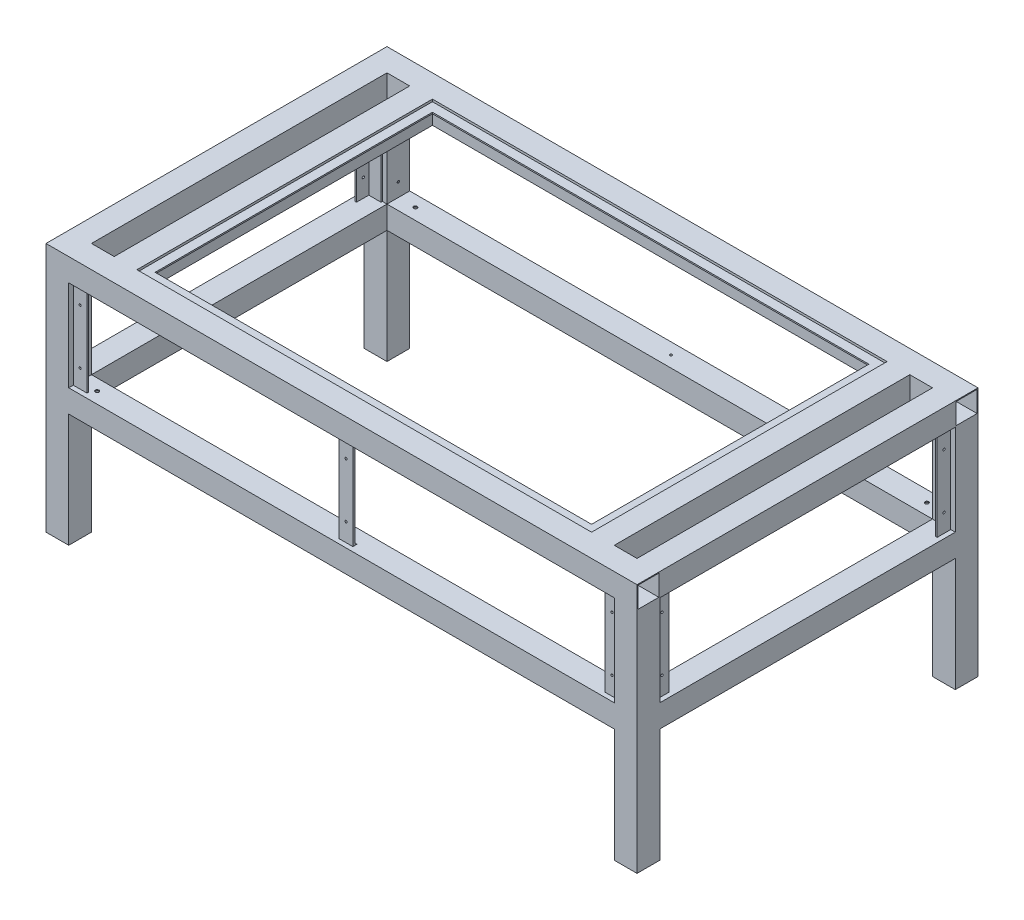
SolidWorks part; units mm, degrees
ref_plane "Plan de face" through (0, 0, 0) normal (0, 0, 1) x (1, 0, 0)
ref_plane "Plan de dessus" through (0, 0, 0) normal (0, 1, 0) x (1, 0, 0)
ref_plane "Plan de droite" through (0, 0, 0) normal (1, 0, 0) x (0, 0, -1)
sketch "Esquisse1" plane through (0, 0, 0) normal (0, 1, 0) x (1, 0, 0)
  line L1 (0, 0) -> (1300, 0)
  line L2 (0, 0) -> (0, 750)
  line L3 (0, 750) -> (1300, 750)
  line L4 (1300, 0) -> (1300, 750)
  line L5 (50, 700) -> (1250, 700)
  line L6 (50, 700) -> (50, 50)
  line L7 (50, 50) -> (1250, 50)
  line L8 (1250, 700) -> (1250, 50)
  dimension "D1" = 1300
  dimension "D2" = 750
  dimension "D3" = 50
  dimension "D4" = 50
  dimension "D5" = 50
  dimension "D6" = 50
extrude "Boss.-Extru.1" add sketch "Esquisse1" against normal blind 550
sketch "Esquisse2" plane through (0, 0, 0) normal (0, 0, 1) x (1, 0, 0)
  line L0 (0, 0) -> (1300, 0) construction
  line L1 (50, -50) -> (1250, -50)
  line L2 (50, -50) -> (50, -250)
  line L3 (50, -250) -> (1250, -250)
  line L4 (1250, -50) -> (1250, -250)
  line L5 (50, -300) -> (1250, -300)
  line L6 (50, -300) -> (50, -550)
  line L7 (50, -550) -> (1250, -550)
  line L8 (1250, -300) -> (1250, -550)
  line L9 (0, -550) -> (1300, -550) construction
  line L10 (1300, -550) -> (1300, 0) construction
  line L11 (0, -550) -> (0, 0) construction
  point P12 (1250, -425)
  dimension "D1" = 50
  dimension "D2" = 50
  dimension "D3" = 200
  dimension "D4" = 0
  dimension "D5" = 50
  dimension "D6" = 50
  dimension "D7" = 50
  dimension "D8" = 50
extrude "Enlèv. mat.-Extru.1" cut sketch "Esquisse2" against normal through all
sketch "Esquisse3" plane through (0, 0, 0) normal (-1, 0, 0) x (0, 0, 1)
  line L0 (-750, -550) -> (0, -550) construction
  line L1 (-700, -50) -> (-50, -50)
  line L2 (-700, -50) -> (-700, -250)
  line L3 (-700, -250) -> (-50, -250)
  line L4 (-50, -50) -> (-50, -250)
  line L5 (-700, -300) -> (-50, -300)
  line L6 (-700, -300) -> (-700, -550)
  line L7 (-700, -550) -> (-50, -550)
  line L8 (-50, -300) -> (-50, -550)
  line L9 (-750, 0) -> (0, 0) construction
  line L10 (0, -550) -> (0, 0) construction
  line L11 (-750, -550) -> (-750, 0) construction
  dimension "D1" = 50
  dimension "D2" = 50
  dimension "D3" = 50
  dimension "D4" = 50
  dimension "D5" = 50
  dimension "D6" = 200
  dimension "D7" = 50
extrude "Enlèv. mat.-Extru.2" cut sketch "Esquisse3" against normal through all
sketch "Esquisse4" plane through (0, 0, 0) normal (0, 1, 0) x (1, 0, 0)
  line L0 (1250, 700) -> (50, 700) construction
  line L1 (100, 700) -> (150, 700)
  line L2 (100, 700) -> (100, 50)
  line L3 (100, 50) -> (150, 50)
  line L4 (150, 700) -> (150, 50)
  line L5 (50, 50) -> (1250, 50) construction
  line L6 (50, 700) -> (50, 50) construction
  line L7 (1150, 700) -> (1200, 700)
  line L8 (1150, 700) -> (1150, 50)
  line L9 (1150, 50) -> (1200, 50)
  line L10 (1200, 700) -> (1200, 50)
  line L11 (1250, 50) -> (1250, 700) construction
  dimension "D1" = 50
  dimension "D2" = 50
  dimension "D3" = 50
  dimension "D4" = 50
extrude "Boss.-Extru.2" add sketch "Esquisse4" against normal blind 50 separate body
sketch "Esquisse18" plane through (0, -250, 0) normal (0, 1, 0) x (1, 0, 0)
  line L0 (50, 0) -> (1250, 0) construction
  line L1 (50, 750) -> (1250, 750) construction
  line L2 (1250, 750) -> (1250, 700) construction
  line L3 (50, 750) -> (50, 700) construction
  line L4 (1250, 50) -> (1250, 0) construction
  line L5 (50, 50) -> (50, 0) construction
  circle A0 centre (1212.5, 25) radius 4
  circle A1 centre (87.5, 25) radius 4
  circle A2 centre (87.5, 725) radius 4
  circle A3 centre (1212.5, 725) radius 4
  dimension "D1" = 8
  dimension "D2" = 8
  dimension "D3" = 8
  dimension "D4" = 8
  dimension "D5" = 1125
  dimension "D6" = 1125
  dimension "D7" = 25
  dimension "D8" = 25
  dimension "D9" = 25
  dimension "D10" = 25
  dimension "D11" = 700
  dimension "D12" = 700
  dimension "D13" = 37.5
  dimension "D14" = 37.5
  dimension "D15" = 37.5
  dimension "D16" = 37.5
extrude "Enlèv. mat.-Extru.5" cut sketch "Esquisse18" against normal blind 80
sketch "Esquisse19" plane through (0, -300, 0) normal (0, -1, 0) x (-1, 0, 0)
  circle A0 centre (-1212.5, 725) radius 15
  circle A1 centre (-87.5, 725) radius 15
  circle A2 centre (-87.5, 25) radius 15
  circle A3 centre (-1212.5, 25) radius 15
  dimension "D1" = 30
  dimension "D2" = 30
  dimension "D3" = 30
  dimension "D4" = 30
extrude "Enlèv. mat.-Extru.6" cut sketch "Esquisse19" against normal blind 48
sketch "Esquisse20" plane through (0, 0, 0) normal (-1, 0, 0) x (0, 0, 1)
  line L0 (-750, 0) -> (0, 0) construction
  line L1 (-2, -2) -> (-48, -2)
  line L2 (-2, -2) -> (-2, -48)
  line L3 (-2, -48) -> (-48, -48)
  line L4 (-48, -2) -> (-48, -48)
  line L5 (-702, -2) -> (-748, -2)
  line L6 (-702, -2) -> (-702, -48)
  line L7 (-702, -48) -> (-748, -48)
  line L8 (-748, -2) -> (-748, -48)
  line L9 (-750, -550) -> (-750, 0) construction
  line L10 (0, -550) -> (0, 0) construction
  dimension "D1" = 2
  dimension "D2" = 2
  dimension "D3" = 46
  dimension "D4" = 46
  dimension "D5" = 2
  dimension "D6" = 46
  dimension "D7" = 46
  dimension "D8" = 2
extrude "Enlèv. mat.-Extru.7" cut sketch "Esquisse20" against normal blind 10000
sketch "Esquisse21" plane through (0, -550, 0) normal (0, -1, 0) x (-1, 0, 0)
  line L0 (0, 0) -> (-50, 0) construction
  line L1 (-1252, 2) -> (-1298, 2)
  line L2 (-1252, 2) -> (-1252, 48)
  line L3 (-1252, 48) -> (-1298, 48)
  line L4 (-1298, 2) -> (-1298, 48)
  line L5 (-1252, 702) -> (-1298, 702)
  line L6 (-1252, 702) -> (-1252, 748)
  line L7 (-1252, 748) -> (-1298, 748)
  line L8 (-1298, 702) -> (-1298, 748)
  line L9 (-2, 702) -> (-48, 702)
  line L10 (-2, 702) -> (-2, 748)
  line L11 (-2, 748) -> (-48, 748)
  line L12 (-48, 702) -> (-48, 748)
  line L13 (-2, 2) -> (-48, 2)
  line L14 (-2, 2) -> (-2, 48)
  line L15 (-2, 48) -> (-48, 48)
  line L16 (-48, 2) -> (-48, 48)
  line L17 (-50, 50) -> (-50, 0) construction
  line L18 (-50, 50) -> (0, 50) construction
  line L19 (-50, 700) -> (0, 700) construction
  line L20 (-50, 750) -> (-50, 700) construction
  line L21 (-1300, 700) -> (-1250, 700) construction
  line L22 (-1300, 700) -> (-1300, 750) construction
  line L23 (-1250, 0) -> (-1300, 0) construction
  line L24 (-1300, 0) -> (-1300, 50) construction
  dimension "D1" = 46
  dimension "D2" = 2
  dimension "D3" = 2
  dimension "D4" = 2
  dimension "D5" = 46
  dimension "D6" = 46
  dimension "D7" = 2
  dimension "D8" = 2
  dimension "D9" = 46
  dimension "D10" = 46
  dimension "D11" = 2
  dimension "D12" = 2
  dimension "D13" = 46
  dimension "D14" = 46
  dimension "D15" = 2
  dimension "D16" = 2
extrude "Enlèv. mat.-Extru.8" cut sketch "Esquisse21" against normal blind 500
sketch "Esquisse22" plane through (0, 0, -50) normal (0, 0, -1) x (-1, 0, 0)
  line L0 (-50, -50) -> (0, -50) construction
  line L1 (-10, -50) -> (-40, -50)
  line L2 (-10, -50) -> (-10, -250)
  line L3 (-10, -250) -> (-40, -250)
  line L4 (-40, -50) -> (-40, -250)
  line L5 (-50, -250) -> (0, -250) construction
  line L6 (0, -250) -> (0, -50) construction
  dimension "D1" = 30
  dimension "D2" = 10
extrude "Boss.-Extru.11" add sketch "Esquisse22" along normal blind 3
sketch "Esquisse23" plane through (10, 0, 0) normal (-1, 0, 0) x (0, 0, 1)
  line L2 (-50, -250) -> (-80, -250)
  line L3 (-50, -250) -> (-50, -50)
  line L4 (-50, -50) -> (-80, -50)
  line L5 (-80, -250) -> (-80, -50)
  line L6 (-53, -50) -> (-50, -50) construction
  circle A0 centre (-65, -90) radius 2.5
  circle A1 centre (-65, -210) radius 2.5
  dimension "D2" = 5
  dimension "D3" = 5
  dimension "D1" = 30
  dimension "D4" = 0
  dimension "D5" = 15
  dimension "D6" = 15
  dimension "D7" = 40
  dimension "D8" = 40
extrude "Boss.-Extru.12" add sketch "Esquisse23" against normal blind 3
ref_plane "Plan1" through (0, 0, -375) normal (0, 0, 1) x (1, 0, 0)
ref_plane "Plan2" through (650, 0, 0) normal (-1, 0, 0) x (0, 0, 1)
mirror "Symétrie1" about plane through (0, 0, -375) normal (0, 0, 1) of "Boss.-Extru.12", "Boss.-Extru.11"
mirror "Symétrie2" about plane through (650, 0, 0) normal (-1, 0, 0) of "Symétrie1"
ref_plane "Plan4" through (137.5, 0, 137.5) normal (0.7071, 0, 0.7071) x (0.7071, 0, -0.7071)
ref_plane "Plan5" through (0, 0, 0) normal (-0.7071, 0, -0.7071) x (-0.7071, 0, 0.7071)
mirror "Symétrie3" about plane through (0, 0, 0) normal (-0.7071, 0, -0.7071) of "Boss.-Extru.11", "Boss.-Extru.12"
sketch "Esquisse25" plane through (0, 0, -50) normal (0, 0, -1) x (-1, 0, 0)
  line L0 (-150, -50) -> (-150, 0) construction
  line L1 (-150, -5) -> (-1150, -5)
  line L2 (-150, -5) -> (-150, -25)
  line L3 (-150, -25) -> (-1150, -25)
  line L4 (-1150, -5) -> (-1150, -25)
  line L5 (-1150, -50) -> (-1150, 0) construction
  line L6 (-50, 0) -> (-1250, 0) construction
  dimension "D1" = 5
  dimension "D2" = 20
extrude "Boss.-Extru.14" add sketch "Esquisse25" along normal blind 3
sketch "Esquisse26" plane through (0, -5, 0) normal (0, 1, 0) x (1, 0, 0)
  line L0 (150, 50) -> (150, 700) construction
  line L1 (1150, 50) -> (150, 50)
  line L2 (1150, 50) -> (1150, 70)
  line L3 (1150, 70) -> (150, 70)
  line L4 (150, 50) -> (150, 70)
  dimension "D1" = 0
  dimension "D2" = 20
extrude "Boss.-Extru.15" add sketch "Esquisse26" against normal blind 3
mirror "Symétrie6" about plane through (0, 0, -375) normal (0, 0, 1) of "Boss.-Extru.15", "Boss.-Extru.14"
sketch "Esquisse27" plane through (1150, 0, 0) normal (-1, 0, 0) x (0, 0, 1)
  line L1 (-50, -5) -> (-700, -5)
  line L2 (-50, -5) -> (-50, -25)
  line L3 (-50, -25) -> (-700, -25)
  line L4 (-700, -5) -> (-700, -25)
extrude "Boss.-Extru.16" add sketch "Esquisse27" along normal blind 3
sketch "Esquisse28" plane through (0, -5, 0) normal (0, 1, 0) x (1, 0, 0)
  line L0 (150, 700) -> (1150, 700) construction
  line L1 (1150, 50) -> (1130, 50)
  line L2 (1150, 50) -> (1150, 700)
  line L3 (1150, 700) -> (1130, 700)
  line L4 (1130, 50) -> (1130, 700)
  dimension "D1" = 20
extrude "Boss.-Extru.17" add sketch "Esquisse28" against normal blind 3
mirror "Symétrie7" about plane through (650, 0, 0) normal (-1, 0, 0) of "Boss.-Extru.16", "Boss.-Extru.17"
mirror "Symétrie8" about plane through (650, 0, 0) normal (-1, 0, 0) of "Symétrie3"
sketch "Esquisse29" plane through (1250, 0, 0) normal (-1, 0, 0) x (0, 0, 1)
  line L0 (-750, -250) -> (-750, -50) construction
  line L1 (-750, -50) -> (-700, -50) construction
  line L2 (-750, -250) -> (-700, -250) construction
  circle A0 centre (-725, -220) radius 2.5
  circle A1 centre (-725, -80) radius 2.5
  dimension "D1" = 5
  dimension "D2" = 5
  dimension "D3" = 25
  dimension "D4" = 25
  dimension "D5" = 30
  dimension "D6" = 30
extrude "Enlèv. mat.-Extru.9" cut sketch "Esquisse29" against normal blind 10
mirror "Symétrie9" about plane through (650, 0, 0) normal (-1, 0, 0) of "Enlèv. mat.-Extru.9"
sketch "Esquisse30" plane through (0, -250, 0) normal (0, 1, 0) x (1, 0, 0)
  line L1 (50, 750) -> (1250, 750) construction
  line L2 (650, 302.5) -> (650, -302.5) construction
  circle A0 centre (650, 725) radius 2.5
  dimension "D1" = 5
  dimension "D2" = 25
  dimension "D3" = 0
extrude "Enlèv. mat.-Extru.10" cut sketch "Esquisse30" against normal blind 15
ref_plane "Plan6" through (0, -150, 0) normal (0, -1, 0) x (-1, 0, 0)
mirror "Symétrie10" about plane through (0, -150, 0) normal (0, -1, 0) of "Enlèv. mat.-Extru.10"
sketch "Esquisse31" plane through (0, -250, 0) normal (0, 1, 0) x (1, 0, 0)
  line L0 (50, 0) -> (1250, 0) construction
  line L1 (635, 15) -> (665, 15)
  line L2 (635, 15) -> (635, 10)
  line L3 (635, 10) -> (665, 10)
  line L4 (665, 15) -> (665, 10)
  line L5 (650, 302.5) -> (650, -302.5) construction
  point P6 (650, 10)
  dimension "D1" = 5
  dimension "D2" = 10
  dimension "D3" = 0
  dimension "D4" = 30
extrude "Boss.-Extru.18" add sketch "Esquisse31" along normal blind 200
fillet "Congé1" radius 5 2 edges at (650, -250, -15) (650, -50, -15)
sketch "Esquisse32" plane through (0, 0, -10) normal (0, 0, 1) x (1, 0, 0)
  line L0 (635, -250) -> (665, -250) construction
  line L1 (635, -50) -> (665, -50) construction
  line L2 (635, -50) -> (635, -250) construction
  circle A0 centre (650, -210) radius 2.5
  circle A1 centre (650, -90) radius 2.5
  dimension "D1" = 5
  dimension "D2" = 5
  dimension "D3" = 40
  dimension "D4" = 40
  dimension "D5" = 15
  dimension "D6" = 15
extrude "Enlèv. mat.-Extru.11" cut sketch "Esquisse32" against normal blind 5
